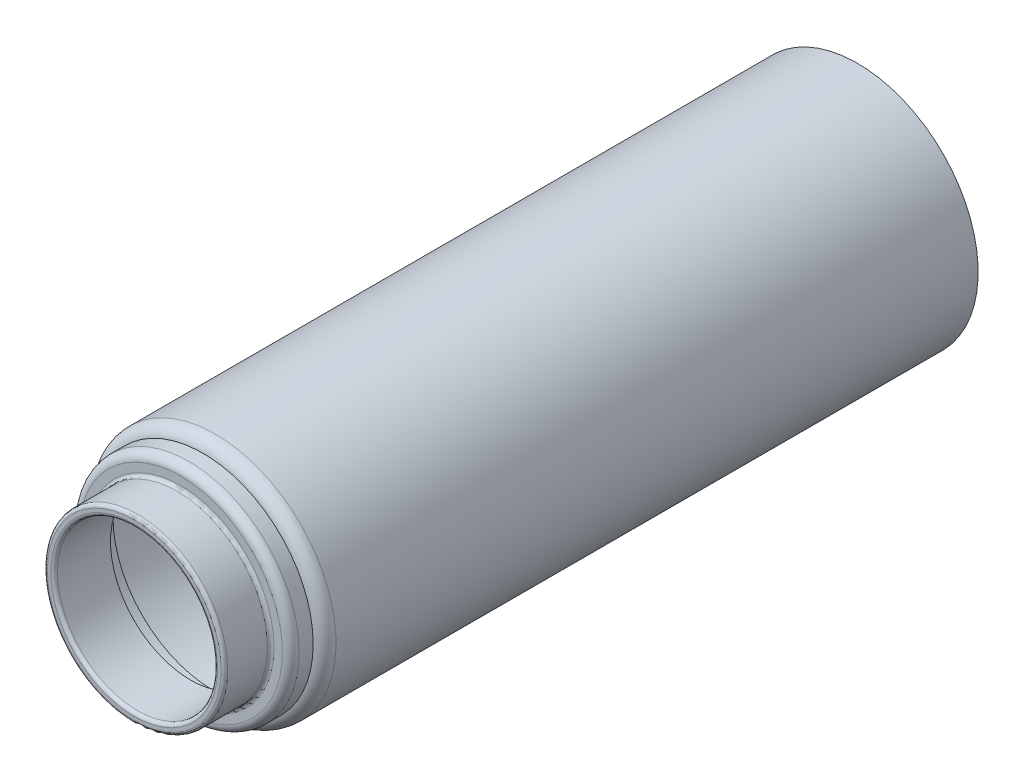
SolidWorks part; units mm, degrees
material "6061 Alloy"
ref_plane "X-Y Datum" through (0, 0, 0) normal (0, 0, 1) x (1, 0, 0)
ref_plane "X-Z Datum" through (0, 0, 0) normal (0, 1, 0) x (1, 0, 0)
ref_plane "Y-Z Datum" through (0, 0, 0) normal (1, 0, 0) x (0, 0, -1)
sketch "Sketch1" plane through (0, 0, 0) normal (0, 0, 1) x (1, 0, 0)
  circle A0 centre (0, 0) radius 36.4046
extrude "Boss-Extrude1" add sketch "Sketch1" along normal blind 197.6438
sketch "Sketch2" plane through (0, 0, 197.6438) normal (0, 0, 1) x (1, 0, 0)
  circle A0 centre (0, 0) radius 33.274
extrude "Boss-Extrude2" add sketch "Sketch2" along normal blind 6.7818
sketch "Sketch3" plane through (0, 0, 204.4256) normal (0, 0, 1) x (1, 0, 0)
  circle A0 centre (0, 0) radius 27.2288
extrude "Boss-Extrude3" add sketch "Sketch3" along normal blind 13.97
shell "Shell1" thickness 3.048 removed face at (27.2288, 0, 218.3956)
fillet "Fillet1" radius 3.81 1 edges at (36.4046, 0, 197.6438)
fillet "Fillet2" radius 2.54 1 edges at (33.274, 0, 204.4256)
fillet "Fillet3" radius 1 1 edges at (27.2288, 0, 204.4256)
fillet "Fillet4" radius 1 2 edges at (27.2288, 0, 218.3956) (24.1808, 0, 218.3956)
